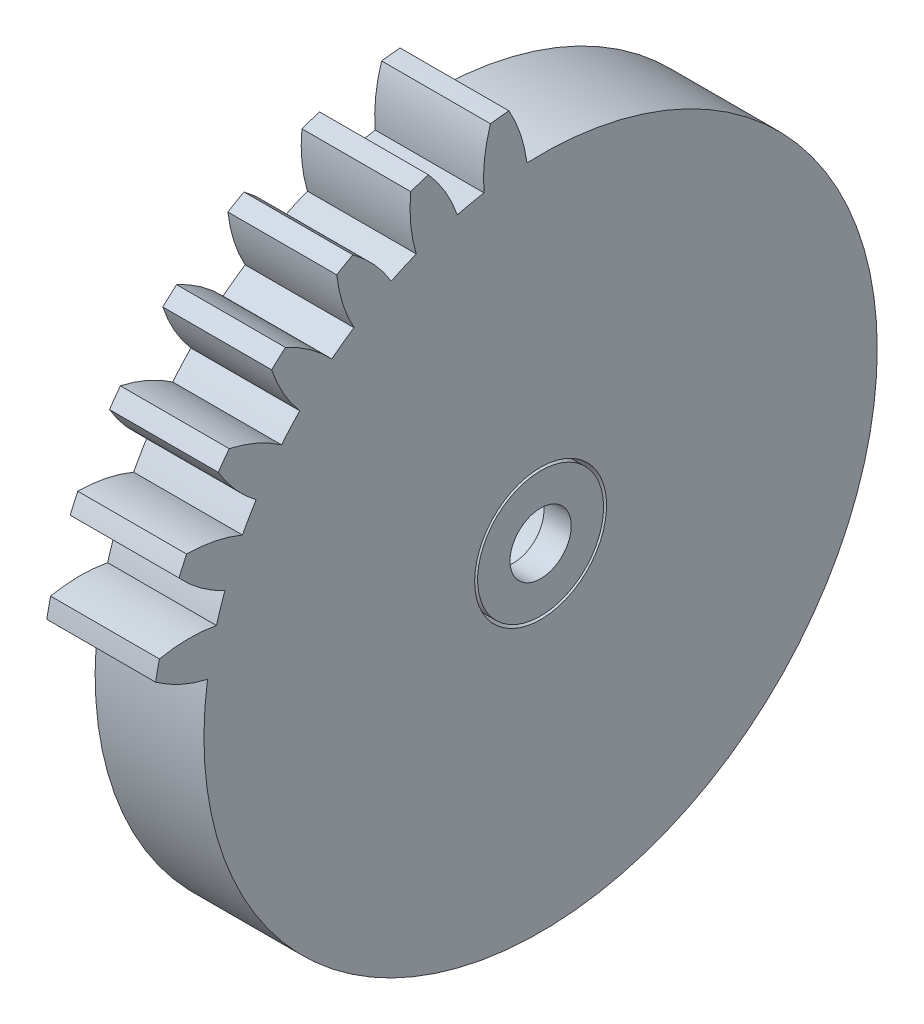
SolidWorks part; units mm, degrees
ref_plane "Plane1" through (0, 0, 0) normal (0, 0, 1) x (1, 0, 0)
ref_plane "Plane2" through (0, 0, 0) normal (0, 1, 0) x (1, 0, 0)
ref_plane "Plane3" through (0, 0, 0) normal (1, 0, 0) x (0, 0, -1)
other "Configuration Table"
sketch "HoldingSke" plane through (0, 0, 0) normal (0, 1, 0) x (1, 0, 0)
  line L0 (0, 0) -> (1.0373, -0.3982)
  line L1 (-15, 0) -> (100, 0) construction
  line L2 (0, 0) -> (-2.1039, 2.3779)
  line L3 (0, 0) -> (-11.863, 4.5341)
  line L4 (0, 0) -> (7.479, 4.318)
  line L5 (0, 0) -> (-46.8476, -17.4728)
  line L6 (0, 0) -> (-8.2896, -5.593)
  line L7 (-2.1039, 2.3779) -> (8.6586, 51.2059)
  line L8 (-76.2, 54.61) -> (-75.5, 54.61)
  line L9 (-67.7845, 28.3722) -> (-49.3413, 33.142)
  line L10 (-76.2, 71.12) -> (104.1128, 71.12)
  line L11 (0, 0) -> (-10, 0)
  line L12 (-76.2, 101.6) -> (-76.166, 101.6)
  line L13 (24.9733, 27.94) -> (52.9518, 28.4284)
  line L14 (24.9733, 27.94) -> (24.9743, 27.94)
  line L15 (24.9733, 27.94) -> (100.4006, 29.5858)
  line L16 (-63.627, -0.9) -> (-12.827, -0.9)
  circle A0 centre (0, 0) radius 2
  circle A1 centre (0, 0) radius 12.374
  circle A2 centre (0, 0) radius 37.5
  circle A3 centre (0, 0) radius 2
  dimension "Num_teeth" = 30
  dimension "Pitch_radius" = 180.3128
  dimension "Width" = 10
  dimension "Thickness" = 10
sketch "BasProSke" plane through (0, 0, 0) normal (0, 1, 0) x (1, 0, 0)
  line L0 (-10, 0) -> (60, 0) construction
  line L1 (0, 0) -> (0, 14.4)
  line L2 (0, 0) -> (4, 0)
  line L3 (4, 0) -> (4, 14.4)
  line L4 (4, 14.4) -> (0, 14.4)
  dimension "Diameter" = 28.8
revolve "Base-Revolve" add sketch "BasProSke" angle 360 about L0
sketch "TooCutSke" plane through (0, 0, 0) normal (1, 0, 0) x (0, 0, -1)
  line L1 (0, 0) -> (0, 107) construction
  line L2 (0, 0) -> (-0.766, 13.4782) construction
  line L3 (0, 0) -> (-2.819, 26.8212) construction
  line L4 (-0.766, 13.4782) -> (-1.4095, 13.4106) construction
  arc A0 (0.502, 12.3638) -> (-0.502, 12.3638) centre (0, 0) ccw
  arc A1 (1.1789, 14.3771) -> (-1.1789, 14.3771) centre (0, 0) ccw
  circle A2 centre (0, 0) radius 13.5 construction
  circle A3 centre (0, 0) radius 13.07 construction
  arc A4 (-0.502, 12.3638) -> (-1.1789, 14.3771) centre (-5.8589, 11.6832) ccw
  arc A5 (1.1789, 14.3771) -> (0.502, 12.3638) centre (5.8589, 11.6832) ccw
extrude "ToothCut" cut sketch "TooCutSke" along normal through all
fillet "Breaks" [suppressed] radius 0.018 tangent propagation no
fillet "RootFillets" [suppressed] radius 0.226
pattern_circular "TeethCuts" count 15 every 12 about axis through (-10, 0, 0) along (1, 0, 0) of "ToothCut"
sketch "HubNeaOneSke" plane through (0, 0, 0) normal (-1, 0, 0) x (0, 0, 1)
  circle A0 centre (0, 0) radius 12.374
  dimension "Diameter" = 24.748
extrude "HubNearOne" [suppressed] add sketch "HubNeaOneSke" along normal blind 40.0001
sketch "HubNeaBotSke" plane through (0, 0, 0) normal (-1, 0, 0) x (0, 0, 1)
  circle A0 centre (0, 0) radius 12.374
  dimension "Diameter" = 24.748
extrude "HubNearBoth" [suppressed] add sketch "HubNeaBotSke" along normal blind 20
ref_plane "FarPln" through (10, 0, 0) normal (1, 0, 0) x (0, 0, -1)
sketch "HubFarSke" plane through (10, 0, 0) normal (1, 0, 0) x (0, 0, -1)
  circle A0 centre (0, 0) radius 12.374
  dimension "Diameter" = 24.748
extrude "HubFar" [suppressed] add sketch "HubFarSke" along normal blind 20
sketch "BorSke" plane through (0, 0, 0) normal (1, 0, 0) x (0, 0, -1)
  circle A0 centre (0, 0) radius 2.425
  dimension "Diameter" = 4.85
extrude "Bore" cut sketch "BorSke" along normal mid plane 100.0001
sketch "KeySke" plane through (0, 0, 0) normal (1, 0, 0) x (0, 0, -1)
  line L0 (-0.8, 0) -> (-0.8, 2.7)
  line L1 (-0.8, 2.7) -> (0.8, 2.7)
  line L2 (0.8, 2.7) -> (0.8, 0)
  line L3 (0, 0) -> (0, 34) construction
  line L4 (-0.8, 0) -> (0.8, 0)
  dimension "Width" = 1.6
extrude "Keyway" [suppressed] cut sketch "KeySke" along normal mid plane 100.0001
pattern_circular "Keyway2" [suppressed] count 2 every 90 about axis through (-10, 0, 0) along (1, 0, 0)
sketch "Sketch1" plane through (4, 0, 0) normal (1, 0, 0) x (0, 0, -1)
  line L0 (0.4203, 12.3669) -> (0.6655, 13.4428)
  line L1 (0.6655, 13.4428) -> (-0.037, 14.8751)
  line L2 (-12.3486, 0.7931) -> (-13.674, 1.0459)
  line L3 (-13.674, 1.0459) -> (-14.854, 0.7931)
  arc A1 (-12.3486, 0.7931) -> (0.4203, 12.3669) centre (0, 0) ccw
  arc A5 (-14.854, 0.7931) -> (-0.037, 14.8751) centre (0, 0) ccw
extrude "Cut-Extrude2" cut sketch "Sketch1" against normal blind 10
sketch "Sketch2" plane through (4, 0, 0) normal (1, 0, 0) x (0, 0, -1)
  circle A0 centre (0, 0) radius 2.315
  dimension "D1" = 4.63
extrude "Boss-Extrude1" add sketch "Sketch2" against normal blind 1
sketch "Sketch3" plane through (3, 0, 0) normal (-1, 0, 0) x (0, 0, 1)
  circle A0 centre (0, 0) radius 1.125
  dimension "D1" = 2.25
extrude "Cut-Extrude3" cut sketch "Sketch3" against normal up to next (1 mm away)
equation "' \"Module@HoldingSke\" = 6.35"
equation "' \"Num_teeth@HoldingSke\" = 12"
equation "' \"Ap@HoldingSke\" =  20"
equation "' \"Ap@HoldingSke\" = 20"
equation "' \"Width@HoldingSke\" = 0.5 * 25.4"
equation "' \"Hub_dia@HoldingSke\"= 1 * 25.4"
equation "' \"Hub_dia@HoldingSke\" = 1 * 25.4"
equation "' \"Overall_len@HoldingSke\" = 1.0 * 25.4"
equation "' \"Bore@HoldingSke\" = 0.75 * 25.4"
equation "' \"T_dim@HoldingSke\" = 0.1 * 25.4"
equation "' \"Width@KeySke\" = 0.25 * 25.4"
equation "' \"Show_teeth@HoldingSke\" = 13"
equation "' \"Backlash@HoldingSke\" = 0.009 * 25.4"
equation "' \"Addendum_fac@HoldingSke\" = 1.0"
equation "' \"Dedendum_fac@HoldingSke\" = 1.25"
equation "' \"Dedendum_add@HoldingSke\" = 0.00005 * 25.4"
equation "' \"Clearance_fac@HoldingSke\" = 0.25"
equation "\"Pitch@HoldingSke\" = 1 / \"Module@HoldingSke\""
equation "\"Overcut_dia@TooCutSke\" = (\"Num_teeth@HoldingSke\" + 2 * \"Addendum_fac@HoldingSke\") / \"Pitch@HoldingSke\" + 0.002 * 25.4"
equation "\"Pitch_dia@TooCutSke\" = \"Num_teeth@HoldingSke\" / \"Pitch@HoldingSke\""
equation "\"Base_dia@TooCutSke\" = \"Num_teeth@HoldingSke\" / \"Pitch@HoldingSke\" * cos((\"Ap@HoldingSke\"  * 3.14159265 / 180))"
equation "\"Root_dia@TooCutSke\" = (\"Num_teeth@HoldingSke\" + 2) / \"Pitch@HoldingSke\" - 2 * (\"Addendum_fac@HoldingSke\" + \"Dedendum_fac@HoldingSke\") / \"Pitch@HoldingSke\" - \"Dedendum_add@HoldingSke\" * 2"
equation "\"Half_ang@TooCutSke\" = 180 / \"Num_teeth@HoldingSke\""
equation "\"Half_CT@TooCutSke\" = \"Num_teeth@HoldingSke\" / \"Pitch@HoldingSke\" * sin((3.14159265 / 2 / \"Num_teeth@HoldingSke\")) / 2 - 7 * \"Backlash@HoldingSke\" / 4"
equation "\"Flank_rad@TooCutSke\" = \"Num_teeth@HoldingSke\" / \"Pitch@HoldingSke\" / 5"
equation "\"Radius@RootFillets\" = \"Clearance_fac@HoldingSke\" / \"Pitch@HoldingSke\" + \"Dedendum_add@HoldingSke\""
equation "\"Break_rad@Breaks\" = 0.02 / \"Pitch@HoldingSke\""
equation "\"Thickness@HoldingSke\" = \"Width@HoldingSke\""
equation "\"OAL@HoldingSke\" = \"Thickness@HoldingSke\""
equation "\"MHD@HoldingSke\" = (\"Num_teeth@HoldingSke\" + 2) / \"Pitch@HoldingSke\" - 2 * (\"Addendum_fac@HoldingSke\" + \"Dedendum_fac@HoldingSke\")  / \"Pitch@HoldingSke\" - \"Dedendum_add@HoldingSke\" * 2"
equation "\"MBD@HoldingSke\" = (\"Num_teeth@HoldingSke\" + 2) / \"Pitch@HoldingSke\" - 2 * (\"Addendum_fac@HoldingSke\" + \"Dedendum_fac@HoldingSke\")  / \"Pitch@HoldingSke\" - \"Dedendum_add@HoldingSke\" * 2 - 0.002 * 25.4"
equation "\"MHD@HoldingSke\" = ((sgn( \"MHD@HoldingSke\" - \"Hub_dia@HoldingSke\" )-1)*( \"MHD@HoldingSke\" - \"Hub_dia@HoldingSke\" ))/-2+ \"Hub_dia@HoldingSke\""
equation "\"MBD@HoldingSke\" = ((sgn( \"MBD@HoldingSke\" - \"Bore@HoldingSke\" )-1)*( \"MBD@HoldingSke\" - \"Bore@HoldingSke\" ))/-2+ \"Bore@HoldingSke\""
equation "\"OAL@HoldingSke\" = ((sgn( \"OAL@HoldingSke\" - \"Overall_len@HoldingSke\" )+1)*( \"OAL@HoldingSke\" - \"Overall_len@HoldingSke\" ))/2 + \"Overall_len@HoldingSke\" + 0.000002 * 25.4"
equation "\"Num_teeth@TeethCuts\" = ((sgn( \"Num_teeth@TeethCuts\" - 2.0)+1)*( \"Num_teeth@TeethCuts\" - 2.0))/2 +2.0"
equation "\"Angle@TeethCuts\" = 360.0 / \"Num_teeth@HoldingSke\""
equation "\"Diameter@BasProSke\" = (\"Num_teeth@HoldingSke\" + 2 * \"Addendum_fac@HoldingSke\") / \"Pitch@HoldingSke\""
equation "' \"Fillet_rad@BasProSke\" =  \"Thickness@HoldingSke\" * 0.05"
equation "' \"Fillet_rad@BasProSke\" = \"Thickness@HoldingSke\" * 0.05"
equation "\"MHD@HoldingSke\" = ((sgn( \"MHD@HoldingSke\" - \"Root_dia@TooCutSke\" )-1)*( \"MHD@HoldingSke\" - \"Root_dia@TooCutSke\" ))/-2+ \"Root_dia@TooCutSke\""
equation "\"Diameter@HubNeaOneSke\" = \"MHD@HoldingSke\""
equation "\"Length@HubNearOne\" = \"OAL@HoldingSke\" - \"Thickness@BasProSke\""
equation "\"Diameter@HubNeaBotSke\" = \"MHD@HoldingSke\""
equation "\"Length@HubNearBoth\" = ( \"OAL@HoldingSke\" - \"Thickness@BasProSke\" ) / 2.0"
equation "\"Thickness@FarPln\" = \"Thickness@BasProSke\""
equation "\"Diameter@HubFarSke\" = \"MHD@HoldingSke\""
equation "\"Length@HubFar\" = ( \"OAL@HoldingSke\" - \"Thickness@BasProSke\" ) / 2.0"
equation "\"D1@Bore\" = \"OAL@HoldingSke\" * 2.0"
equation "\"D1@Keyway\" = \"OAL@HoldingSke\" * 2.0"
equation "\"Offset@KeySke\" = \"T_dim@HoldingSke\" + \"MBD@HoldingSke\" / 2.0"
